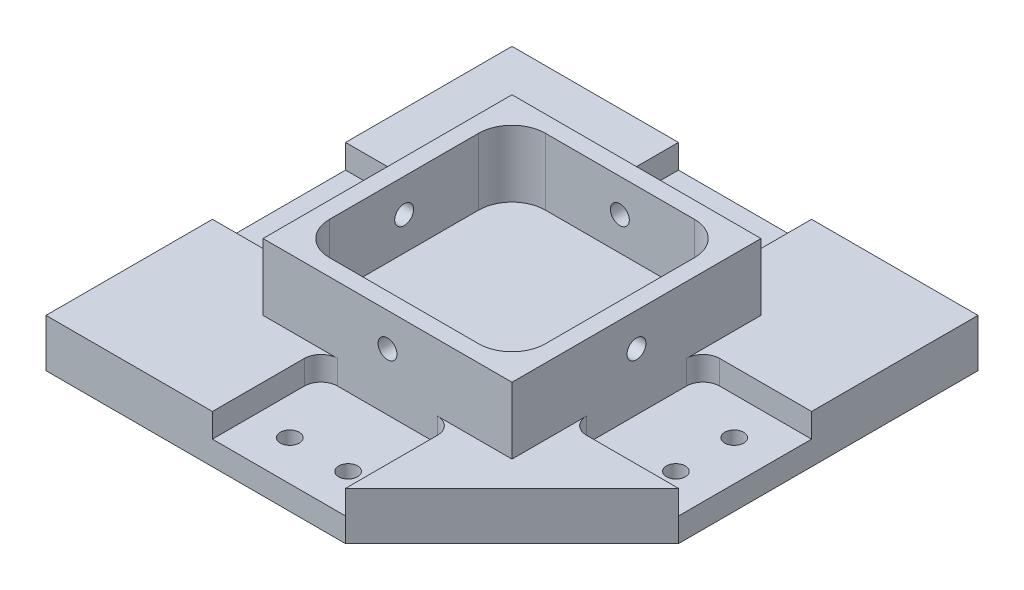
SolidWorks part; units mm, degrees
material "6061 Alloy"
ref_plane "Front Plane" through (0, 0, 0) normal (0, 0, 1) x (1, 0, 0)
ref_plane "Top Plane" through (0, 0, 0) normal (0, 1, 0) x (1, 0, 0)
ref_plane "Right Plane" through (0, 0, 0) normal (1, 0, 0) x (0, 0, -1)
sketch "Sketch1" plane through (0, 0, 0) normal (0, 1, 0) x (1, 0, 0)
  line L1 (0, 0) -> (88.9, 0)
  line L2 (0, 0) -> (0, 88.9)
  line L3 (0, 88.9) -> (88.9, 88.9)
  line L4 (88.9, 0) -> (88.9, 88.9)
  dimension "D1" = 88.9
  dimension "D2" = 88.9
extrude "Boss-Extrude1" add sketch "Sketch1" along normal blind 9.144
sketch "Sketch2" plane through (0, 9.144, 0) normal (0, 1, 0) x (1, 0, 0)
  line L0 (88.9, 88.9) -> (0, 88.9) construction
  line L1 (31.75, 88.9) -> (57.15, 88.9)
  line L2 (31.75, 88.9) -> (31.75, 67.31)
  line L3 (31.75, 67.31) -> (57.15, 67.31)
  line L4 (57.15, 88.9) -> (57.15, 67.31)
  line L5 (0, 88.9) -> (0, 0) construction
  line L6 (0, 57.15) -> (21.59, 57.15)
  line L7 (0, 57.15) -> (0, 31.75)
  line L8 (0, 31.75) -> (21.59, 31.75)
  line L9 (21.59, 57.15) -> (21.59, 31.75)
  line L10 (0, 0) -> (88.9, 0) construction
  line L11 (31.75, 0) -> (57.15, 0)
  line L12 (31.75, 0) -> (31.75, 21.59)
  line L13 (31.75, 21.59) -> (57.15, 21.59)
  line L14 (57.15, 0) -> (57.15, 21.59)
  line L15 (88.9, 0) -> (88.9, 88.9) construction
  line L16 (88.9, 57.15) -> (67.31, 57.15)
  line L17 (88.9, 57.15) -> (88.9, 31.75)
  line L18 (88.9, 31.75) -> (67.31, 31.75)
  line L19 (67.31, 57.15) -> (67.31, 31.75)
  dimension "D1" = 31.75
  dimension "D2" = 25.4
  dimension "D3" = 25.4
  dimension "D4" = 31.75
  dimension "D5" = 25.4
  dimension "D6" = 31.75
  dimension "D7" = 25.4
  dimension "D8" = 31.75
  dimension "D9" = 21.59
  dimension "D10" = 21.59
  dimension "D11" = 21.59
  dimension "D12" = 21.59
extrude "Cut-Extrude1" cut sketch "Sketch2" against normal blind 4.572
sketch "Sketch3" plane through (0, 9.144, 0) normal (0, 1, 0) x (1, 0, 0)
  line L0 (31.75, 88.9) -> (0, 88.9) construction
  line L1 (20.6375, 68.2625) -> (68.2625, 68.2625)
  line L2 (20.6375, 68.2625) -> (20.6375, 20.6375)
  line L3 (20.6375, 20.6375) -> (68.2625, 20.6375)
  line L4 (68.2625, 68.2625) -> (68.2625, 20.6375)
  line L5 (0, 31.75) -> (0, 0) construction
  line L6 (88.9, 31.75) -> (88.9, 57.15) construction
  line L7 (57.15, 88.9) -> (31.75, 88.9) construction
  line L8 (0, 57.15) -> (0, 31.75) construction
  line L9 (31.75, 0) -> (57.15, 0) construction
  circle A0 centre (28.194, 44.45) radius 2.4
  circle A1 centre (44.45, 60.706) radius 2.4
  circle A2 centre (60.706, 44.45) radius 2.4
  circle A3 centre (44.45, 28.194) radius 2.4
  dimension "D5" = 4.8
  dimension "D6" = 4.8
  dimension "D7" = 4.8
  dimension "D8" = 4.8
  dimension "D1" = 47.625
  dimension "D2" = 47.625
  dimension "D3" = 20.6375
  dimension "D4" = 20.6375
  dimension "D9" = 28.194
  dimension "D10" = 28.194
  dimension "D11" = 28.194
  dimension "D12" = 28.194
  dimension "D13" = 23.8125
  dimension "D14" = 23.8125
  dimension "D15" = 23.8125
  dimension "D16" = 23.8125
extrude "Cut-Extrude2" [suppressed] cut sketch "Sketch3" against normal through all contours A2 | A1 | A0 | A3
sketch "Sketch4" plane through (0, 4.572, 0) normal (0, 1, 0) x (1, 0, 0)
  line L0 (0, 57.15) -> (0, 31.75) construction
  line L1 (57.15, 88.9) -> (31.75, 88.9) construction
  line L2 (88.9, 31.75) -> (88.9, 57.15) construction
  line L3 (31.75, 0) -> (57.15, 0) construction
  line L4 (0, 31.75) -> (21.59, 31.75) construction
  line L5 (31.75, 21.59) -> (31.75, 0) construction
  line L6 (67.31, 31.75) -> (88.9, 31.75) construction
  line L7 (57.15, 67.31) -> (57.15, 88.9) construction
  circle A0 centre (81.28, 50.0126) radius 1.8034
  circle A1 centre (81.28, 38.8874) radius 1.8034
  circle A2 centre (50.0126, 81.28) radius 1.8034
  circle A3 centre (38.8874, 81.28) radius 1.8034
  circle A4 centre (7.62, 50.0126) radius 1.8034
  circle A5 centre (7.62, 38.8874) radius 1.8034
  circle A6 centre (38.8874, 7.62) radius 1.8034
  circle A7 centre (50.0126, 7.62) radius 1.8034
  point P24 (0, 0)
  dimension "D1" = 3.6068
  dimension "D2" = 3.6068
  dimension "D3" = 3.6068
  dimension "D4" = 3.6068
  dimension "D5" = 3.6068
  dimension "D6" = 3.6068
  dimension "D7" = 3.6068
  dimension "D8" = 3.6068
  dimension "D9" = 7.62
  dimension "D10" = 7.62
  dimension "D11" = 7.62
  dimension "D12" = 7.62
  dimension "D13" = 7.62
  dimension "D14" = 7.62
  dimension ".313" = 7.62
  dimension "D16" = 7.62
  dimension "D17" = 11.1252
  dimension "D18" = 7.1374
  dimension "D19" = 7.1374
  dimension "D20" = 11.1252
  dimension "D21" = 7.1374
  dimension "D22" = 11.1252
  dimension "D23" = 7.1374
  dimension "D24" = 11.1252
extrude "Cut-Extrude3" cut sketch "Sketch4" against normal through all
sketch "Sketch5" plane through (0, 9.144, 0) normal (0, 1, 0) x (1, 0, 0)
  line L0 (88.9, 88.9) -> (57.15, 88.9) construction
  line L1 (88.9, 31.75) -> (88.9, 57.15) construction
  circle A0 centre (44.45, 44.45) radius 6.35
  dimension "D1" = 12.7
  dimension "D2" = 44.45
  dimension "D3" = 44.45
extrude "Cut-Extrude4" [suppressed] cut sketch "Sketch5" against normal through all
sketch "Sketch6" plane through (0, 9.144, 0) normal (0, 1, 0) x (1, 0, 0)
  line L0 (88.9, 31.75) -> (57.15, 0)
  line L1 (57.15, 0) -> (88.9, 0)
  line L2 (88.9, 0) -> (88.9, 31.75)
extrude "Cut-Extrude5" cut sketch "Sketch6" against normal through all
sketch "Sketch7" plane through (0, 9.144, 0) normal (0, 1, 0) x (1, 0, 0)
  line L0 (0, 88.9) -> (0, 57.15) construction
  line L1 (20.701, 68.199) -> (68.199, 68.199)
  line L2 (20.701, 68.199) -> (20.701, 20.701)
  line L3 (20.701, 20.701) -> (68.199, 20.701)
  line L4 (68.199, 68.199) -> (68.199, 20.701)
  line L5 (0, 0) -> (31.75, 0) construction
  line L7 (23.876, 23.876) -> (65.024, 23.876)
  line L8 (23.876, 23.876) -> (23.876, 65.024)
  line L9 (23.876, 65.024) -> (65.024, 65.024)
  line L10 (65.024, 23.876) -> (65.024, 65.024)
  dimension "D1" = 47.498
  dimension "D2" = 47.498
  dimension "D3" = 20.701
  dimension "D4" = 20.701
  dimension "D5" = 3.175
  dimension "D6" = 3.175
  dimension "D7" = 3.175
  dimension "D8" = 3.175
extrude "Boss-Extrude2" add sketch "Sketch7" along normal blind 12.7 and the other way up to next (4.572 mm away)
fillet "Fillet9" radius 6.35 1 edges at (65.024, 15.494, -23.876)
fillet "Fillet10" radius 6.35 1 edges at (23.876, 15.494, -23.876)
fillet "Fillet11" radius 6.35 1 edges at (65.024, 15.494, -65.024)
fillet "Fillet12" radius 6.35 1 edges at (23.876, 15.494, -65.024)
fillet "Fillet15" radius 3.175 1 edges at (20.701, 6.858, -57.15)
fillet "Fillet16" radius 3.175 1 edges at (31.75, 6.858, -20.701)
fillet "Fillet17" radius 3.175 1 edges at (57.15, 6.858, -20.701)
fillet "Fillet18" radius 3.175 1 edges at (68.199, 6.858, -57.15)
fillet "Fillet19" radius 3.175 1 edges at (68.199, 6.858, -31.75)
fillet "Fillet20" radius 3.175 1 edges at (31.75, 6.858, -68.199)
fillet "Fillet21" radius 3.175 1 edges at (57.15, 6.858, -68.199)
fillet "Fillet22" radius 3.175 1 edges at (20.701, 6.858, -31.75)
sketch "Sketch9" plane through (0, 0, -68.199) normal (0, 0, -1) x (-1, 0, 0)
  line L0 (-68.199, 21.844) -> (-68.199, 9.144) construction
  line L1 (-68.199, 21.844) -> (-20.701, 21.844) construction
  circle A0 centre (-44.45, 15.494) radius 1.8034
  dimension "D1" = 3.6068
  dimension "D2" = 23.749
  dimension "D3" = 6.35
extrude "Cut-Extrude6" cut sketch "Sketch9" against normal through all
sketch "Sketch10" plane through (68.199, 0, 0) normal (1, 0, 0) x (0, 0, -1)
  line L0 (20.701, 21.844) -> (68.199, 21.844) construction
  line L1 (20.701, 21.844) -> (20.701, 9.144) construction
  circle A0 centre (44.45, 15.494) radius 1.8034
  dimension "D1" = 3.6068
  dimension "D2" = 6.35
  dimension "D3" = 23.749
extrude "Cut-Extrude7" cut sketch "Sketch10" against normal through all
equation "\"hinge_hole\"= 0.142in"
equation "\"D1@Sketch4\"=\"hinge_hole\""
equation "\"D2@Sketch4\"=\"hinge_hole\""
equation "\"D3@Sketch4\"=\"hinge_hole\""
equation "\"D4@Sketch4\"=\"hinge_hole\""
equation "\"D5@Sketch4\"=\"hinge_hole\""
equation "\"D6@Sketch4\"=\"hinge_hole\""
equation "\"D7@Sketch4\"=\"hinge_hole\""
equation "\"D8@Sketch4\"=\"hinge_hole\""
equation "\"hinge_hole_dist\"= 0.297 + 0.25"
equation "\".313@Sketch4\"=.3"
equation "\"hinge_hole_sep\"=0.438"
equation "\"hinge_hole_from_wall\"= ( 1 - \"hinge_hole_sep\" ) / 2"
equation "\"D17@Sketch4\"=\"hinge_hole_sep\""
equation "\"D18@Sketch4\"=\"hinge_hole_from_wall\""
equation "\"D19@Sketch4\"=\"hinge_hole_from_wall\""
equation "\"D20@Sketch4\"=\"hinge_hole_sep\""
equation "\"D21@Sketch4\"=\"hinge_hole_from_wall\""
equation "\"D22@Sketch4\"=\"hinge_hole_sep\""
equation "\"D23@Sketch4\"=\"hinge_hole_from_wall\""
equation "\"D24@Sketch4\"=\"hinge_hole_sep\""
equation "\"D9@Sketch2\"=\"hinge_hole_dist\" + (0.6-0.297)"
equation "\"D12@Sketch2\"=\"hinge_hole_dist\" + (0.6-0.297)"
equation "\"D11@Sketch2\"=\"hinge_hole_dist\" + (0.6-0.297)"
equation "\"D10@Sketch2\"=\"hinge_hole_dist\" + (0.6-0.297)"
